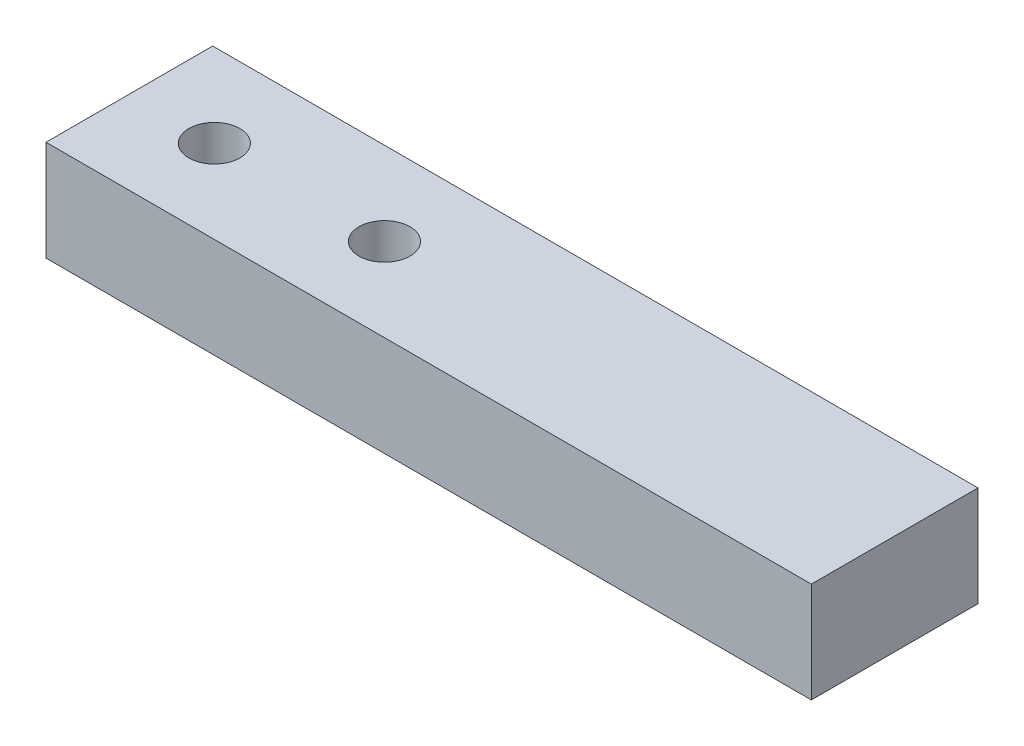
SolidWorks part; units mm, degrees
ref_plane "Front Plane" through (0, 0, 0) normal (0, 0, 1) x (1, 0, 0)
ref_plane "Top Plane" through (0, 0, 0) normal (0, 1, 0) x (1, 0, 0)
ref_plane "Right Plane" through (0, 0, 0) normal (1, 0, 0) x (0, 0, -1)
sketch "Sketch1" plane through (0, 0, 0) normal (0, 1, 0) x (1, 0, 0)
  line L1 (-22.5, -4.9) -> (22.5, -4.9)
  line L2 (-22.5, -4.9) -> (-22.5, 4.9)
  line L3 (-22.5, 4.9) -> (22.5, 4.9)
  line L4 (22.5, -4.9) -> (22.5, 4.9)
  line L5 (-22.5, -4.9) -> (22.5, 4.9) construction
  line L6 (-22.5, 4.9) -> (22.5, -4.9) construction
  circle A0 centre (-17.5, 0) radius 1.5
  circle A1 centre (-7.5, 0) radius 1.5
  point P0 (0, 0)
  point P10 (-22.5, 0)
  point P12 (-18.3219, -0.675)
  dimension "D3" = 3
  dimension "D1" = 9.8
  dimension "D2" = 45
  dimension "D4" = 10
  dimension "D5" = 5
extrude "Boss-Extrude1" add sketch "Sketch1" along normal blind 5.9
